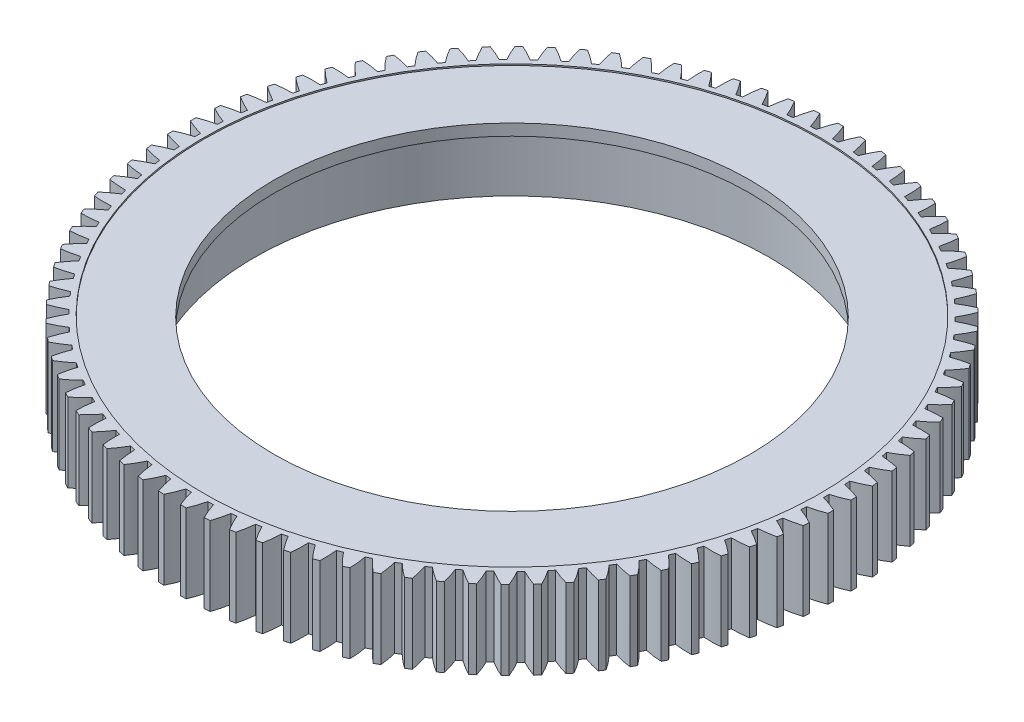
SolidWorks part; units mm, degrees
ref_plane "Front Plane" through (0, 0, 0) normal (0, 0, 1) x (1, 0, 0)
ref_plane "Top Plane" through (0, 0, 0) normal (0, 1, 0) x (1, 0, 0)
ref_plane "Right Plane" through (0, 0, 0) normal (1, 0, 0) x (0, 0, -1)
ref_plane "Plane1" through (0, 0, 0) normal (0, 0, -1) x (-1, 0, 0)
sketch "Sketch5" plane through (0, 0, 0) normal (0, 0, -1) x (-1, 0, 0)
  line L0 (-227.695, -54) -> (0, -54)
  line L1 (0, -54) -> (0, 0)
  line L2 (0, 0) -> (-227.695, 0)
  line L3 (-227.695, 0) -> (-227.695, -54)
  line L4 (0, -54) -> (0, 0) construction
revolve "Revolve1" add sketch "Sketch5" angle 360 about L4 reverse direction yes
ref_plane "Plane2" through (0, 0, 137.8858) normal (0, 0, -1) x (-1, 0, 0)
sketch "Sketch6" plane through (0, 0, 137.8858) normal (0, 0, -1) x (-1, 0, 0)
  line L0 (-141.2093, -54) -> (-137.8858, -54)
  line L1 (-137.8858, -54) -> (-137.8858, -36)
  line L2 (-137.8858, -36) -> (-141.2093, -37.997)
  line L3 (-141.2093, -37.997) -> (-141.2093, -42)
  line L4 (-141.2093, -42) -> (-141.2093, -54)
  line L5 (-137.8858, -54) -> (-137.8858, -36) construction
revolve "Cut-Revolve1" cut sketch "Sketch6" angle 360 about L5 reverse direction yes
ref_plane "Plane3" through (0, 0, 50.4697) normal (0, 0, -1) x (-1, 0, 0)
sketch "Sketch7" plane through (0, 0, 50.4697) normal (0, 0, -1) x (-1, 0, 0)
  line L0 (-191.679, -54) -> (-188.3555, -54)
  line L1 (-188.3555, -54) -> (-188.3555, -36)
  line L2 (-188.3555, -36) -> (-191.679, -37.997)
  line L3 (-191.679, -37.997) -> (-191.679, -42)
  line L4 (-191.679, -42) -> (-191.679, -54)
  line L5 (-188.3555, -54) -> (-188.3555, -36) construction
revolve "Cut-Revolve2" cut sketch "Sketch7" angle 360 about L5 reverse direction yes
ref_plane "Plane4" through (0, 0, -50.4697) normal (0, 0, -1) x (-1, 0, 0)
sketch "Sketch8" plane through (0, 0, -50.4697) normal (0, 0, -1) x (-1, 0, 0)
  line L0 (-191.679, -54) -> (-188.3555, -54)
  line L1 (-188.3555, -54) -> (-188.3555, -36)
  line L2 (-188.3555, -36) -> (-191.679, -37.997)
  line L3 (-191.679, -37.997) -> (-191.679, -42)
  line L4 (-191.679, -42) -> (-191.679, -54)
  line L5 (-188.3555, -54) -> (-188.3555, -36) construction
revolve "Cut-Revolve3" cut sketch "Sketch8" angle 360 about L5 reverse direction yes
ref_plane "Plane5" through (0, 0, -137.8858) normal (0, 0, -1) x (-1, 0, 0)
sketch "Sketch9" plane through (0, 0, -137.8858) normal (0, 0, -1) x (-1, 0, 0)
  line L0 (-141.2093, -54) -> (-137.8858, -54)
  line L1 (-137.8858, -54) -> (-137.8858, -36)
  line L2 (-137.8858, -36) -> (-141.2093, -37.997)
  line L3 (-141.2093, -37.997) -> (-141.2093, -42)
  line L4 (-141.2093, -42) -> (-141.2093, -54)
  line L5 (-137.8858, -54) -> (-137.8858, -36) construction
revolve "Cut-Revolve4" cut sketch "Sketch9" angle 360 about L5 reverse direction yes
ref_plane "Plane6" through (0, 0, -188.3555) normal (0, 0, -1) x (-1, 0, 0)
sketch "Sketch10" plane through (0, 0, -188.3555) normal (0, 0, -1) x (-1, 0, 0)
  line L0 (-53.7932, -54) -> (-50.4697, -54)
  line L1 (-50.4697, -54) -> (-50.4697, -36)
  line L2 (-50.4697, -36) -> (-53.7932, -37.997)
  line L3 (-53.7932, -37.997) -> (-53.7932, -42)
  line L4 (-53.7932, -42) -> (-53.7932, -54)
  line L5 (-50.4697, -54) -> (-50.4697, -36) construction
revolve "Cut-Revolve5" cut sketch "Sketch10" angle 360 about L5 reverse direction yes
sketch "Sketch11" plane through (0, 0, -188.3555) normal (0, 0, -1) x (-1, 0, 0)
  line L0 (47.1462, -54) -> (50.4697, -54)
  line L1 (50.4697, -54) -> (50.4697, -36)
  line L2 (50.4697, -36) -> (47.1462, -37.997)
  line L3 (47.1462, -37.997) -> (47.1462, -42)
  line L4 (47.1462, -42) -> (47.1462, -54)
  line L5 (50.4697, -54) -> (50.4697, -36) construction
revolve "Cut-Revolve6" cut sketch "Sketch11" angle 360 about L5 reverse direction yes
sketch "Sketch12" plane through (0, 0, -137.8858) normal (0, 0, -1) x (-1, 0, 0)
  line L0 (134.5623, -54) -> (137.8858, -54)
  line L1 (137.8858, -54) -> (137.8858, -36)
  line L2 (137.8858, -36) -> (134.5623, -37.997)
  line L3 (134.5623, -37.997) -> (134.5623, -42)
  line L4 (134.5623, -42) -> (134.5623, -54)
  line L5 (137.8858, -54) -> (137.8858, -36) construction
revolve "Cut-Revolve7" cut sketch "Sketch12" angle 360 about L5 reverse direction yes
sketch "Sketch13" plane through (0, 0, -50.4697) normal (0, 0, -1) x (-1, 0, 0)
  line L0 (185.032, -54) -> (188.3555, -54)
  line L1 (188.3555, -54) -> (188.3555, -36)
  line L2 (188.3555, -36) -> (185.032, -37.997)
  line L3 (185.032, -37.997) -> (185.032, -42)
  line L4 (185.032, -42) -> (185.032, -54)
  line L5 (188.3555, -54) -> (188.3555, -36) construction
revolve "Cut-Revolve8" cut sketch "Sketch13" angle 360 about L5 reverse direction yes
sketch "Sketch14" plane through (0, 0, 50.4697) normal (0, 0, -1) x (-1, 0, 0)
  line L0 (185.032, -54) -> (188.3555, -54)
  line L1 (188.3555, -54) -> (188.3555, -36)
  line L2 (188.3555, -36) -> (185.032, -37.997)
  line L3 (185.032, -37.997) -> (185.032, -42)
  line L4 (185.032, -42) -> (185.032, -54)
  line L5 (188.3555, -54) -> (188.3555, -36) construction
revolve "Cut-Revolve9" cut sketch "Sketch14" angle 360 about L5 reverse direction yes
sketch "Sketch15" plane through (0, 0, 137.8858) normal (0, 0, -1) x (-1, 0, 0)
  line L0 (134.5623, -54) -> (137.8858, -54)
  line L1 (137.8858, -54) -> (137.8858, -36)
  line L2 (137.8858, -36) -> (134.5623, -37.997)
  line L3 (134.5623, -37.997) -> (134.5623, -42)
  line L4 (134.5623, -42) -> (134.5623, -54)
  line L5 (137.8858, -54) -> (137.8858, -36) construction
revolve "Cut-Revolve10" cut sketch "Sketch15" angle 360 about L5 reverse direction yes
ref_plane "Plane7" through (0, 0, 188.3555) normal (0, 0, -1) x (-1, 0, 0)
sketch "Sketch16" plane through (0, 0, 188.3555) normal (0, 0, -1) x (-1, 0, 0)
  line L0 (47.1462, -54) -> (50.4697, -54)
  line L1 (50.4697, -54) -> (50.4697, -36)
  line L2 (50.4697, -36) -> (47.1462, -37.997)
  line L3 (47.1462, -37.997) -> (47.1462, -42)
  line L4 (47.1462, -42) -> (47.1462, -54)
  line L5 (50.4697, -54) -> (50.4697, -36) construction
revolve "Cut-Revolve11" cut sketch "Sketch16" angle 360 about L5 reverse direction yes
sketch "Sketch17" plane through (0, 0, 188.3555) normal (0, 0, -1) x (-1, 0, 0)
  line L0 (-53.7932, -54) -> (-50.4697, -54)
  line L1 (-50.4697, -54) -> (-50.4697, -36)
  line L2 (-50.4697, -36) -> (-53.7932, -37.997)
  line L3 (-53.7932, -37.997) -> (-53.7932, -42)
  line L4 (-53.7932, -42) -> (-53.7932, -54)
  line L5 (-50.4697, -54) -> (-50.4697, -36) construction
revolve "Cut-Revolve12" cut sketch "Sketch17" angle 360 about L5 reverse direction yes
hole_wizard "Hole1" positions "Sketch19" profile "Sketch18" legacy
sketch "Sketch19" plane through (0, -54, 0) normal (0, -1, 0) x (-1, 0, 0)
  point P0 (0, 0)
sketch "Sketch18" plane through (0, -54, 0) normal (1, 0, 0) x (0, 0, -1)
  line L0 (0, 0) -> (0, 54)
  line L1 (0, 54) -> (166, 54)
  line L2 (166, 54) -> (166, 46)
  line L3 (166, 46) -> (180, 46)
  line L4 (180, 46) -> (180, 0)
  line L5 (180, 0) -> (0, 0)
  line L6 (0, 110) -> (0, -10) construction
  dimension "Diameter" = 332
  dimension "Depth" = 54
  dimension "C-Bore Diameter" = 360
  dimension "C-Bore Depth" = 46
sketch "Sketch24" plane through (0, -54, 0) normal (0, -1, 0) x (1, 0, 0)
  circle A0 centre (0, 0) radius 230
  circle A1 centre (0, 0) radius 215.1265
  dimension "D1" = 460
extrude "Boss-Extrude1" add sketch "Sketch24" against normal blind 55
sketch "Sketch23" plane through (0, -54, 0) normal (0, -1, 0) x (1, 0, 0)
  line L0 (0, 0) -> (224.975, 3.3533) construction
  line L1 (0, 0) -> (224.953, -4.5996) construction
  circle A0 centre (0, 0) radius 230 construction
  circle A1 centre (0, 0) radius 225 construction
  circle A2 centre (0, 0) radius 211.4308 construction
  circle A3 centre (0, 0) radius 218.75 construction
  arc A4 (218.7461, 1.3081) -> (218.7355, -2.5199) centre (0, 0) cw
  arc A6 (241.6676, 11.7674) -> (241.5987, -13.106) centre (0, 0) cw
  spline S0 degree 4 poles (217.2456, 0.9231) (217.3479, 0.948) (217.5455, 0.9964) (217.8587, 1.0729) (218.5879, 1.2641) (218.9934, 1.3745) (219.9977, 1.6591) (220.6216, 1.8514) (221.4757, 2.1169) (222.1863, 2.3536) (222.9789, 2.6223) (223.717, 2.8855) (224.4833, 3.1656) (225.2277, 3.4486) (225.9805, 3.7424) (226.7236, 4.0419) (227.552, 4.3847) (228.559, 4.8148) (229.7456, 5.3408) (231.104, 5.9698) (232.5519, 6.6707) (233.9856, 7.3942) (235.2331, 8.0491) (236.2902, 8.6212) (237.1736, 9.1114) (237.8643, 9.5007) (238.5787, 9.9116) (239.2426, 10.298) (239.9855, 10.7403) (240.5834, 11.0991) (241.556, 11.6965) (241.9916, 11.9688) (243.0036, 12.6069) (243.3411, 12.8287) (243.682, 13.0479) (243.8066, 13.1293) knots 0 0 0 0 0 0.013145 0.02629 0.05258 0.079962 0.107344 0.134726 0.162108 0.18949 0.216872 0.244254 0.271636 0.299018 0.3264 0.353782 0.381164 0.420996 0.47576 0.530524 0.585288 0.640051 0.694815 0.722197 0.749579 0.776961 0.804343 0.831725 0.859107 0.886489 0.913871 0.956935 0.978468 1 1 1 1 1 construction
  spline S1 degree 4 poles (218.7461, 1.3081) (218.9131, 1.3535) (219.2369, 1.4435) (219.9977, 1.6591) (220.6216, 1.8514) (221.4757, 2.1169) (222.1863, 2.3536) (222.9789, 2.6223) (223.717, 2.8855) (224.4833, 3.1656) (225.2277, 3.4486) (225.9805, 3.7424) (226.7236, 4.0419) (227.552, 4.3847) (228.559, 4.8148) (229.7456, 5.3408) (231.104, 5.9698) (232.5519, 6.6707) (233.9856, 7.3942) (235.2331, 8.0491) (236.2902, 8.6212) (237.1736, 9.1114) (237.8643, 9.5007) (238.5787, 9.9116) (239.2426, 10.298) (239.9855, 10.7403) (240.5834, 11.0991) (241.2215, 11.491) (241.5206, 11.676) (241.6676, 11.7674) knots 0.052581 0.052581 0.052581 0.052581 0.052581 0.079962 0.107344 0.134726 0.162108 0.18949 0.216872 0.244254 0.271636 0.299018 0.3264 0.353782 0.381164 0.420996 0.47576 0.530524 0.585288 0.640051 0.694815 0.722197 0.749579 0.776961 0.804343 0.831725 0.859107 0.886489 0.91387 0.91387 0.91387 0.91387 0.91387
  spline S2 degree 4 poles (218.7355, -2.5199) (218.8431, -2.5498) (219.0626, -2.6116) (219.4894, -2.7336) (219.9473, -2.8701) (220.4852, -3.0343) (221.0463, -3.2117) (221.8165, -3.463) (222.6382, -3.7438) (223.4786, -4.0434) (224.3322, -4.3606) (225.0438, -4.6331) (225.9292, -4.9824) (226.9866, -5.4152) (228.5624, -6.0888) (230.6419, -7.0362) (232.6945, -8.0408) (234.7203, -9.0979) (236.7248, -10.1947) (238.5353, -11.2307) (239.9976, -12.1078) (241.1226, -12.8062) (241.5987, -13.106) knots 0.03181 0.03181 0.03181 0.03181 0.03181 0.036358 0.040905 0.045453 0.050001 0.056092 0.062183 0.074366 0.081188 0.08801 0.094831 0.101653 0.115296 0.128939 0.156226 0.183512 0.197155 0.210798 0.238085 0.25824 0.25824 0.25824 0.25824 0.25824
  dimension "D1" = 460
  dimension "D2" = 450
  dimension "D3" = 422.8617
  dimension "D4" = 437.5
  dimension "D5" = 2.025
extrude "Cut-Extrude2" cut sketch "Sketch23" against normal through all
pattern_circular "CirPattern1" count 90 over 360 about axis through (0, -54, 0) along (0, -1, 0) of "Cut-Extrude2"
ref_axis "Axis1" through (0, -8, 0) along (0, -1, 0)
equation "\"phi\"= 20"
equation "\"m\"= 5"
equation "\"Np\"= 15"
equation "\"Ng\"= 90"
equation "\"adndm_p\"= \"m\""
equation "\"ddndm_p\"= 1.25 * \"m\""
equation "\"dp\"= \"m\" * \"Np\""
equation "\"dg\"= \"m\" * \"Ng\""
equation "\"adndm_g\"= \"m\""
equation "\"ddndm_g\"= 1.25 * \"m\""
equation "\"majorDia_p\"= \"dp\" + 2 * \"m\""
equation "\"majorDia_g\"= \"dg\" + 2 * \"m\""
equation "\"rootDia_p\"= \"dp\" - 2.5 * \"m\""
equation "\"rootDia_g\"= \"dg\" - 2.5 * \"m\""
equation "\"baseDia_p\"= \"dp\" * cos ( \"phi\" )"
equation "\"baseDia_g\"= \"dg\" * cos ( \"phi\" )"
equation "\"clearance\"= \"ddndm_g\" - \"adndm_g\""
equation "\"D1@Sketch23\"=\"majorDia_g\""
equation "\"D2@Sketch23\"=\"dg\""
equation "\"D3@Sketch23\"=\"baseDia_g\""
equation "\"D4@Sketch23\"=\"rootDia_g\""
equation "\"theta_ht_g\"= 360 / 3.95 / \"Ng\""
equation "\"D1@CirPattern1\"=\"Ng\""
equation "\"D1@Sketch24\"=\"majorDia_g\""
equation "\"D5@Sketch23\"=2*\"theta_ht_g\""
